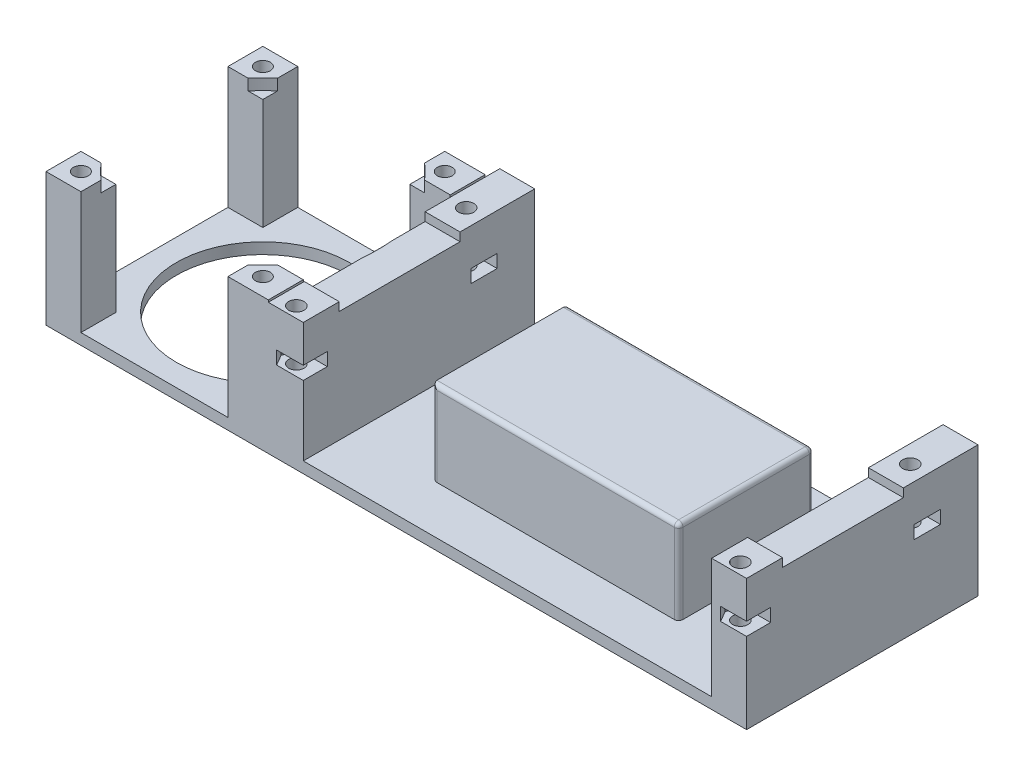
SolidWorks part; units mm, degrees
ref_plane "Front Plane" through (0, 0, 0) normal (0, 0, 1) x (1, 0, 0)
ref_plane "Top Plane" through (0, 0, 0) normal (0, 1, 0) x (1, 0, 0)
ref_plane "Right Plane" through (0, 0, 0) normal (1, 0, 0) x (0, 0, -1)
sketch "Sketch1" plane through (0, 0, 0) normal (0, 1, 0) x (1, 0, 0)
  line L0 (-1192.9506, 281.3201) -> (-294.8846, 281.3201) construction
  line L9 (0, 0) -> (-231, 0) construction
  line L10 (-231, 0) -> (-231, 53)
  line L11 (-231, 53) -> (-121.4859, 53)
  line L12 (-121.4859, 53) -> (-121.4859, 0)
  line L13 (-227.0835, 41.4) -> (-231, 41.4) construction
  line L14 (-227.0835, 41.4) -> (-227.0835, 53) construction
  line L15 (-231, 0) -> (-121.4859, 0)
  circle A0 centre (-227.0835, 41.4) radius 1.75
  circle A1 centre (-227.0835, 2.5016) radius 1.75
  circle A2 centre (-125.4059, 41.4) radius 1.75
  circle A3 centre (-125.4059, 2.5016) radius 1.75
  dimension "D3" = 3.5
  dimension "D1" = 231
  dimension "D2" = 53
  dimension "D4" = 3.9165
  dimension "D5" = 11.6
  dimension "D9" = 3.92
  dimension "D10" = 109.5141
  dimension "D11" = 2.5016
extrude "Boss-Extrude1" add sketch "Sketch1" along normal blind 30
sketch "Sketch2" plane through (0, 0, 0) normal (0, 0, 1) x (1, 0, 0)
  line L0 (-231, 30) -> (-121.4859, 30) construction
  line L1 (-223, 30) -> (-129.4859, 30)
  line L2 (-223, 30) -> (-223, 2.54)
  line L3 (-223, 2.54) -> (-129.4859, 2.54)
  line L4 (-129.4859, 30) -> (-129.4859, 2.54)
  line L5 (-176.243, 30) -> (-176.243, 0) construction
  line L6 (-231, 0) -> (-121.4859, 0) construction
  line L7 (-231, 30) -> (-231, 0) construction
  line L8 (-121.4859, 30) -> (-121.4859, 0) construction
  point P10 (-176.243, 2.54)
  dimension "D1" = 8
  dimension "D2" = 2.54
  dimension "D3" = 8
extrude "Cut-Extrude1" cut sketch "Sketch2" against normal through all
ref_plane "Plane1" through (0, 20, 0) normal (0, 1, 0) x (1, 0, 0)
sketch "Sketch4" plane through (0, 2.54, 0) normal (0, 1, 0) x (1, 0, 0)
  line L0 (-176.243, 53) -> (-176.243, 0) construction
  line L1 (-223, 26.5) -> (-129.4859, 26.5) construction
  line L3 (-202.913, 12.53) -> (-149.573, 12.53)
  line L4 (-223, 0) -> (-129.4859, 0)
  line L5 (-129.4859, 0) -> (-129.4859, 53)
  line L6 (-129.4859, 53) -> (-223, 53)
  line L7 (-223, 53) -> (-223, 0)
  line L8 (-223, 0) -> (-129.4859, 0) construction
  line L9 (-129.4859, 0) -> (-129.4859, 53) construction
  line L10 (-129.4859, 53) -> (-223, 53) construction
  line L11 (-223, 53) -> (-223, 0) construction
  line L12 (-202.913, 12.53) -> (-202.913, 40.47)
  line L13 (-202.913, 40.47) -> (-149.573, 40.47)
  line L14 (-149.573, 12.53) -> (-149.573, 40.47)
  line L15 (-202.913, 12.53) -> (-149.573, 40.47) construction
  line L16 (-202.913, 40.47) -> (-149.573, 12.53) construction
  point P8 (-176.243, 26.5)
  dimension "D2" = 53.34
  dimension "D3" = 27.94
  dimension "D1" = 0
extrude "Cut-Extrude3" cut sketch "Sketch4" against normal through all contours L3 L14 L13 L12
sketch "Sketch5" plane through (0, 2.54, 0) normal (0, 1, 0) x (1, 0, 0)
  line L0 (-149.573, 12.53) -> (-149.573, 40.47) construction
  line L1 (-202.913, 12.53) -> (-149.573, 12.53) construction
  line L2 (-202.913, 12.53) -> (-202.913, 40.47) construction
  line L3 (-202.913, 40.47) -> (-149.573, 40.47) construction
  line L4 (-149.573, 12.53) -> (-149.573, 40.47)
  line L5 (-202.913, 12.53) -> (-149.573, 12.53)
  line L6 (-202.913, 12.53) -> (-202.913, 40.47)
  line L7 (-202.913, 40.47) -> (-149.573, 40.47)
  line L9 (-204.413, 11.03) -> (-148.073, 11.03)
  line L10 (-204.413, 11.03) -> (-204.413, 41.97)
  line L11 (-204.413, 41.97) -> (-148.073, 41.97)
  line L12 (-148.073, 11.03) -> (-148.073, 41.97)
  dimension "D1" = 1.5
  dimension "D2" = 1.5
  dimension "D3" = 1.5
  dimension "D4" = 1.5
extrude "Boss-Extrude2" add sketch "Sketch5" along normal blind 17.78
sketch "Sketch6" plane through (0, 20.32, 0) normal (0, 1, 0) x (1, 0, 0)
  line L1 (-204.413, 41.97) -> (-148.073, 41.97)
  line L2 (-204.413, 41.97) -> (-204.413, 11.03)
  line L3 (-204.413, 11.03) -> (-148.073, 11.03)
  line L4 (-148.073, 41.97) -> (-148.073, 11.03)
extrude "Boss-Extrude3" add sketch "Sketch6" along normal blind 1.5
sketch "Sketch7" plane through (0, 0, -40.47) normal (0, 0, 1) x (1, 0, 0)
  line L0 (-223, 2.54) -> (-129.4859, 2.54) construction
  line L1 (-149.573, 20.32) -> (-157.193, 20.32)
  line L2 (-149.573, 20.32) -> (-149.573, 2.54)
  line L3 (-149.573, 2.54) -> (-157.193, 2.54)
  line L4 (-157.193, 20.32) -> (-157.193, 2.54)
  dimension "D1" = 7.62
extrude "Cut-Extrude4" cut sketch "Sketch7" against normal through all
sketch "Sketch9" plane through (-202.913, 0, 0) normal (1, 0, 0) x (0, 0, -1)
  line L0 (41.97, 2.54) -> (11.03, 2.54) construction
  line L1 (41.97, 2.54) -> (11.03, 2.54) construction
  line L2 (40.47, 0) -> (40.47, 20.32) construction
  line L4 (40.47, 0) -> (40.47, 20.32) construction
  line L5 (12.53, 0) -> (12.53, 20.32) construction
  line L11 (17.53, 0.54) -> (35.47, 0.54)
  line L20 (17.53, 0.54) -> (17.53, 2.79)
  line L21 (17.53, 2.79) -> (35.47, 2.79)
  line L22 (35.47, 0.54) -> (35.47, 2.79)
  dimension "D1" = 5
  dimension "D2" = 5
  dimension "D3" = 0.5
  dimension "D4" = 4
extrude "Cut-Extrude5" cut sketch "Sketch9" against normal blind 5
sketch "Sketch10" plane through (0, 0, 0) normal (0, -1, 0) x (1, 0, 0)
  line L0 (-149.573, -12.53) -> (-149.573, -40.47) construction
  line L1 (-149.573, -32.47) -> (-141.573, -32.47)
  line L2 (-149.573, -32.47) -> (-149.573, -20.53)
  line L3 (-149.573, -20.53) -> (-141.573, -20.53)
  line L4 (-141.573, -32.47) -> (-141.573, -20.53)
  line L5 (-202.913, -12.53) -> (-149.573, -12.53) construction
  line L6 (-202.913, -40.47) -> (-149.573, -40.47) construction
  dimension "D1" = 8
  dimension "D2" = 8
  dimension "D3" = 8
extrude "Cut-Extrude6" cut sketch "Sketch10" against normal up to surface (2.54 mm away) up to face at (-178.5963, 2.54, -31.4067)
sketch "Sketch13" plane through (0, 0, 0) normal (0, -1, 0) x (1, 0, 0)
  line L0 (-202.913, -12.53) -> (-149.573, -12.53) construction
  line L1 (-149.573, -7.53) -> (-159.573, -7.53)
  line L2 (-149.573, -7.53) -> (-149.573, -45.47)
  line L3 (-149.573, -45.47) -> (-159.573, -45.47)
  line L4 (-159.573, -7.53) -> (-159.573, -45.47)
  line L5 (-202.913, -40.47) -> (-149.573, -40.47) construction
  line L6 (-149.573, -12.53) -> (-149.573, -20.53) construction
  point P10 (-149.573, -16.53)
  dimension "D1" = 10
  dimension "D2" = 5
  dimension "D3" = 5
extrude "Cut-Extrude8" cut sketch "Sketch13" against normal blind 1
fillet "Fillet2" radius 1 13 edges at (-157.193, 11.43, -40.47) (-148.073, 2.54, -26.5) (-149.573, 2.54, -26.5) (-207.913, 2.54, -26.5) (-204.413, 2.79, -26.5) (-157.193, 11.43, -41.97) (-176.243, 21.82, -41.97) (-204.413, 12.18, -41.97) (-148.073, 12.18, -41.97) (-148.073, 21.82, -26.5) (-148.073, 12.18, -11.03) (-176.243, 21.82, -11.03) (-204.413, 12.18, -11.03)
sketch "Sketch11" plane through (-231, 0, 0) normal (-1, 0, 0) x (0, 0, 1)
  line L0 (-53, 30) -> (0, 30) construction
  line L1 (-35.903, 30) -> (-8.242, 30)
  line L2 (-35.903, 30) -> (-35.903, 28.0566)
  line L3 (-35.903, 28.0566) -> (-8.242, 28.0566)
  line L4 (-8.242, 30) -> (-8.242, 28.0566)
extrude "Cut-Extrude7" cut sketch "Sketch11" against normal through all
sketch "Sketch14" plane through (0, 0, 0) normal (0, -1, 0) x (1, 0, 0)
  line L1 (-231, 0) -> (-281.91, 0)
  line L2 (-231, 0) -> (-231, -49.656)
  line L3 (-231, -49.656) -> (-281.91, -49.656)
  line L4 (-281.91, 0) -> (-281.91, -49.656)
  line L5 (-277.906, -4) -> (-236.25, -4) construction
  line L6 (-277.906, -4) -> (-277.906, -45.656) construction
  line L7 (-277.906, -45.656) -> (-236.25, -45.656) construction
  line L8 (-236.25, -4) -> (-236.25, -45.656) construction
  line L9 (-277.906, -4) -> (-236.25, -45.656) construction
  line L10 (-277.906, -45.656) -> (-236.25, -4) construction
  circle A0 centre (-257.078, -24.828) radius 19.812
  circle A1 centre (-277.906, -45.656) radius 1.7
  circle A2 centre (-236.25, -45.656) radius 1.7
  circle A3 centre (-236.25, -4) radius 1.7
  circle A4 centre (-277.906, -4) radius 1.7
  dimension "D3" = 3.4
  dimension "D4" = 39.624
  dimension "D1" = 50.91
  dimension "D2" = 49.656
  dimension "D5" = 41.656
  dimension "D6" = 41.656
  dimension "D7" = 4
  dimension "D8" = 5.25
extrude "Boss-Extrude4" add sketch "Sketch14" against normal blind 2.54
sketch "Sketch15" plane through (0, 2.54, 0) normal (0, 1, 0) x (1, 0, 0)
  line L0 (-231, 0) -> (-281.91, 0) construction
  line L1 (-281.91, 49.656) -> (-273.91, 49.656)
  line L2 (-281.91, 49.656) -> (-281.91, 41.656)
  line L3 (-281.91, 41.656) -> (-273.91, 41.656)
  line L4 (-273.91, 49.656) -> (-273.91, 41.656)
  line L5 (-231, 49.656) -> (-240.25, 49.656)
  line L6 (-231, 49.656) -> (-231, 41.656)
  line L7 (-231, 41.656) -> (-240.25, 41.656)
  line L8 (-240.25, 49.656) -> (-240.25, 41.656)
  line L9 (-231, 0) -> (-240.25, 0)
  line L10 (-231, 0) -> (-231, 8)
  line L11 (-231, 8) -> (-240.25, 8)
  line L12 (-240.25, 0) -> (-240.25, 8)
  line L13 (-281.91, 0) -> (-273.91, 0)
  line L14 (-281.91, 0) -> (-281.91, 8)
  line L15 (-281.91, 8) -> (-273.91, 8)
  line L16 (-273.91, 0) -> (-273.91, 8)
  line L17 (-281.91, 0) -> (-281.91, 49.656) construction
  circle A0 centre (-277.906, 4) radius 1.7 construction
  circle A1 centre (-236.25, 4) radius 1.7 construction
  circle A2 centre (-236.25, 45.656) radius 1.7 construction
  circle A3 centre (-277.906, 45.656) radius 1.7 construction
  circle A4 centre (-277.906, 4) radius 1.7
  circle A5 centre (-236.25, 4) radius 1.7
  circle A6 centre (-236.25, 45.656) radius 1.7
  circle A7 centre (-277.906, 45.656) radius 1.7
  dimension "D1" = 8
  dimension "D2" = 8
  dimension "D3" = 8
  dimension "D4" = 8
  dimension "D5" = 8
  dimension "D6" = 8
  dimension "D7" = 4
  dimension "D8" = 4
extrude "Boss-Extrude5" add sketch "Sketch15" along normal blind 27.94
sketch "Sketch16" plane through (0, 30.48, 0) normal (0, 1, 0) x (1, 0, 0)
  circle A0 centre (-257.078, 24.828) radius 19.812 construction
  circle A1 centre (-257.078, 24.828) radius 19.812 construction
  circle A2 centre (-257.078, 24.828) radius 26.289
  dimension "D1" = 52.578
extrude "Cut-Extrude9" cut sketch "Sketch16" against normal blind 2.54
sketch "Sketch3" plane through (0, 20, 0) normal (0, 1, 0) x (1, 0, 0)
  line L0 (-123.6739, 5.5016) -> (-121.4859, 5.5016)
  line L1 (-127.138, -0.4984) -> (-123.6739, -0.4984)
  line L2 (-123.6739, -0.4984) -> (-121.9418, 2.5016) construction
  line L3 (-121.9418, 2.5016) -> (-123.6739, 5.5016) construction
  line L4 (-123.6739, 5.5016) -> (-127.138, 5.5016)
  line L5 (-127.138, 5.5016) -> (-128.8701, 2.5016)
  line L6 (-128.8701, 2.5016) -> (-127.138, -0.4984)
  line L7 (-121.4859, 0) -> (-121.4859, 8.242) construction
  line L8 (-121.4859, 5.5016) -> (-121.4859, -0.4984)
  line L9 (-121.4859, -0.4984) -> (-123.6739, -0.4984)
  line L10 (-223, 53) -> (-129.4859, 53) construction
  line L12 (-223, 53) -> (-129.4859, 53) construction
  line L13 (-227.0835, 41.4) -> (-227.0835, 2.5016) construction
  line L14 (-176.243, 53) -> (-176.243, -2.5637) construction
  line L15 (-227.0835, 21.9508) -> (-176.243, 21.9508) construction
  line L16 (-228.8121, 5.5016) -> (-231, 5.5016) construction
  line L17 (-231, 5.5016) -> (-231, -0.4984) construction
  line L18 (-231, -0.4984) -> (-228.8121, -0.4984) construction
  line L19 (-225.3479, -0.4984) -> (-228.8121, -0.4984) construction
  line L20 (-223.6159, 2.5016) -> (-225.3479, -0.4984) construction
  line L21 (-225.3479, 5.5016) -> (-223.6159, 2.5016) construction
  line L22 (-228.8121, 5.5016) -> (-225.3479, 5.5016) construction
  line L23 (-121.4859, 44.4) -> (-123.6739, 44.4)
  line L24 (-121.4859, 38.4) -> (-121.4859, 44.4)
  line L25 (-128.8701, 41.4) -> (-127.138, 44.4)
  line L26 (-127.138, 38.4) -> (-128.8701, 41.4)
  line L27 (-123.6739, 38.4) -> (-127.138, 38.4)
  line L28 (-127.138, 44.4) -> (-123.6739, 44.4)
  line L29 (-123.6739, 38.4) -> (-121.4859, 38.4)
  line L30 (-228.8121, 38.4) -> (-225.3479, 38.4) construction
  line L31 (-225.3479, 38.4) -> (-223.6159, 41.4) construction
  line L32 (-223.6159, 41.4) -> (-225.3479, 44.4) construction
  line L33 (-225.3479, 44.4) -> (-228.8121, 44.4) construction
  line L34 (-231, 44.4) -> (-228.8121, 44.4) construction
  line L35 (-231, 38.4) -> (-231, 44.4) construction
  line L36 (-228.8121, 38.4) -> (-231, 38.4) construction
  line L37 (-228.8121, 5.5016) -> (-230.5458, 2.5046)
  line L38 (-230.5458, 2.5046) -> (-228.8173, -0.4954)
  line L39 (-228.8173, -0.4954) -> (-225.3479, -0.4984)
  line L43 (-228.8121, 44.4) -> (-230.5458, 41.403)
  line L44 (-230.5458, 41.403) -> (-228.8173, 38.403)
  line L45 (-228.8173, 38.403) -> (-225.3479, 38.4)
  line L49 (-223.6211, 41.397) -> (-225.3497, 44.397) [skipped]
  line L50 (-225.3549, 38.4) -> (-223.6211, 41.397) [skipped]
  line L51 (-223.6211, 2.4986) -> (-225.3497, 5.4986) [skipped]
  line L52 (-225.3549, -0.4984) -> (-223.6211, 2.4986) [skipped]
  line L53 (-223, 53) -> (-223, 35.903) construction
  line L54 (-228.8121, 44.4) -> (-223, 44.4)
  line L55 (-223, 38.4) -> (-225.3479, 38.4)
  line L56 (-228.8121, 5.5016) -> (-222.995, 5.5016)
  line L58 (-222.995, 5.5016) -> (-222.995, -0.4984)
  line L59 (-222.995, -0.4984) -> (-225.3479, -0.4984)
  line L60 (-223.1957, 44.3951) -> (-228.8121, 44.4) [skipped]
  line L61 (-223, 44.4) -> (-223, 38.4)
  line L63 (-225.3497, 5.4986) -> (-228.8121, 5.5016) [skipped]
  circle A0 centre (-227.0835, 41.4) radius 1.75 construction
  circle A1 centre (-227.0835, 2.5016) radius 1.75 construction
  circle A2 centre (-125.4059, 41.4) radius 1.75 construction
  circle A3 centre (-125.4059, 2.5016) radius 1.75 construction
  circle A4 centre (-227.0835, 41.4) radius 1.75 construction
  circle A5 centre (-227.0835, 2.5016) radius 1.75 construction
  circle A6 centre (-125.4059, 41.4) radius 1.75 construction
  circle A7 centre (-125.4059, 2.5016) radius 1.75 construction
  circle A8 centre (-125.4059, 2.5016) radius 3 construction
  circle A9 centre (-227.0835, 2.5016) radius 2.9985 construction
  circle A10 centre (-227.0835, 41.4) radius 2.9985 construction
  dimension "D1" = 6
extrude "Cut-Extrude2" cut sketch "Sketch3" against normal mid plane 3
sketch "Sketch17" plane through (0, 0, 0) normal (0, -1, 0) x (1, 0, 0)
  line L0 (-141.573, -32.47) -> (-141.573, -20.53) construction
  line L1 (-149.573, -32.47) -> (-141.573, -32.47) construction
  line L2 (-141.573, -20.53) -> (-141.573, -32.47)
  arc A0 (-141.573, -20.53) -> (-141.573, -32.47) centre (-141.573, -26.5) cw
extrude "Cut-Extrude11" cut sketch "Sketch17" against normal blind 1
